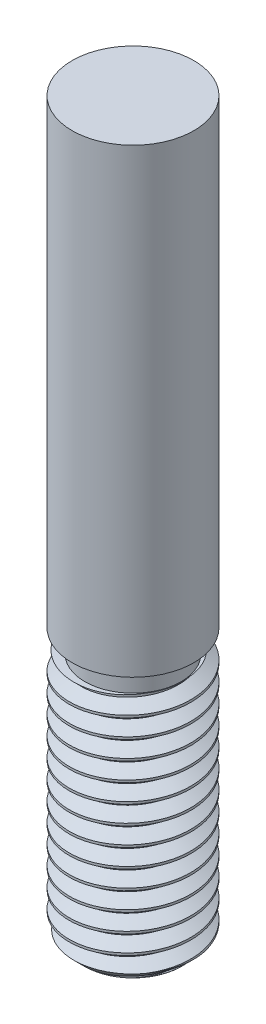
SolidWorks part; units mm, degrees
ref_plane "Front Plane" through (0, 0, 0) normal (0, 0, 1) x (1, 0, 0)
ref_plane "Top Plane" through (0, 0, 0) normal (0, 1, 0) x (1, 0, 0)
ref_plane "Right Plane" through (0, 0, 0) normal (1, 0, 0) x (0, 0, -1)
sketch "Sketch2" plane through (0, 0, 0) normal (0, 0, 1) x (1, 0, 0)
  line L0 (0, -1.5875) -> (0, -77.7875)
  line L1 (6.35, -1.5875) -> (0, -1.5875)
  line L7 (6.35, -1.5875) -> (6.35, -77.7875)
  line L8 (6.35, -77.7875) -> (0, -77.7875)
  dimension "D1" = 6.35
  dimension "D2" = 76.2
revolve "Shaft" add sketch "Sketch2" angle 360 about L0
ref_plane "Plane1" through (0, 12.7, 0) normal (0, 1, 0) x (1, 0, 0)
ref_plane "Plane2" through (0, 0, 12.7) normal (0, 0, 1) x (1, 0, 0)
chamfer "End" distance 1.27 angle 45 1 edges at (-6.35, -77.7875, 0)
sketch "Sketch10" plane through (0, -77.7875, 0) normal (0, -1, 0) x (1, 0, 0)
  circle A0 centre (0, 0) radius 6.35
curve "Helix/Spiral1" pitch 1.9538 height 27.3538 radius 6.35 centre (0, -77.7875, 0) axis (0, 1, 0) start towards (0, 0, 1)
sketch "Sketch11" plane through (0, 0, 0) normal (1, 0, 0) x (0, 0, -1)
  line L0 (-6.35, -77.0543) -> (-6.35, -79.0081) construction
  line L1 (-6.35, -79.0081) -> (-6.35, -78.7644) construction
  line L2 (-6.35, -78.7644) -> (-6.944, -78.7644)
  line L3 (-6.35, -78.7644) -> (-5.08, -78.0312)
  line L4 (-5.08, -78.0312) -> (-5.08, -77.7875)
  line L5 (-5.08, -77.7875) -> (-6.35, -77.0543)
  line L6 (-6.944, -78.7644) -> (-6.944, -77.0543)
  line L7 (-6.944, -77.0543) -> (-6.35, -77.0543)
  line L8 (-5.08, -77.7875) -> (5.08, -77.7875) construction
  line L19 (-6.35, -1.5875) -> (-6.35, -76.5175) construction
  dimension "D1" = 1.9538
  dimension "D2" = 60
  dimension "D3" = 60
  dimension "D4" = 1.27
sweep "Threads" cut profiles "Sketch11" path "Helix/Spiral1"
sketch "Sketch12" plane through (0, 0, 0) normal (-1, 0, 0) x (0, 0, 1)
  line L2 (5.0165, -49.7004) -> (7.6835, -49.7004)
  line L3 (5.0165, -49.7004) -> (5.0165, -52.0817)
  line L4 (5.0165, -52.0817) -> (7.6835, -52.0817)
  line L5 (7.6835, -49.7004) -> (7.6835, -52.0817)
  point P0 (6.35, -49.7004)
  dimension "D1" = 2.667
  dimension "D2" = 2.3813
revolve "Inset" cut sketch "Sketch12" angle 360 about axis through (0, -1.5875, 0) along (0, 1, 0)
